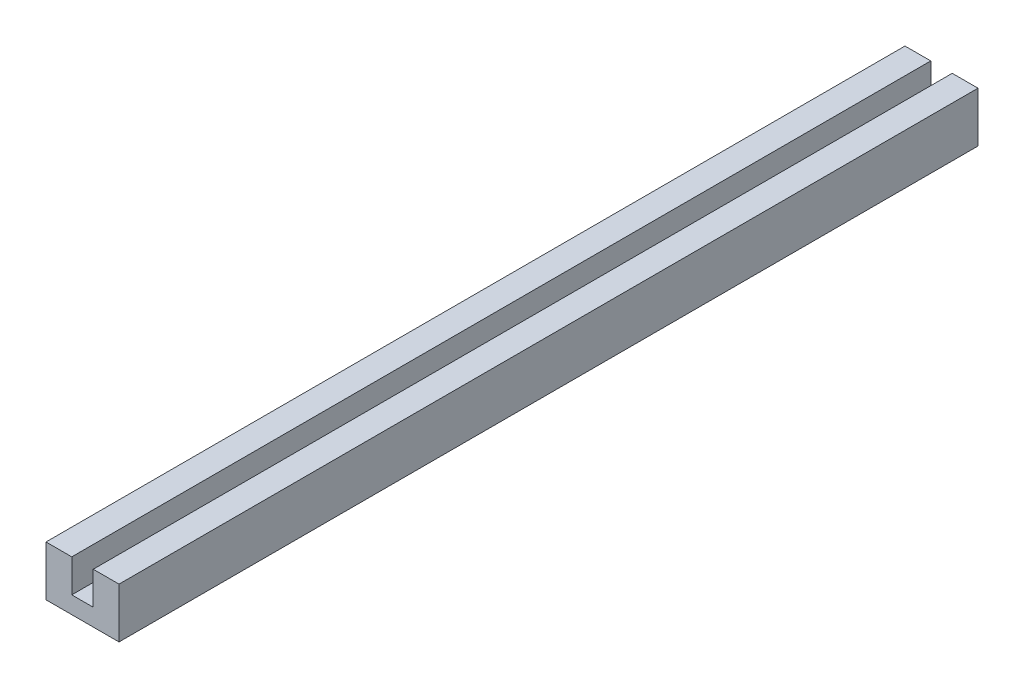
SolidWorks part; units mm, degrees
ref_plane "Front Plane" through (0, 0, 0) normal (0, 0, 1) x (1, 0, 0)
ref_plane "Top Plane" through (0, 0, 0) normal (0, 1, 0) x (1, 0, 0)
ref_plane "Right Plane" through (0, 0, 0) normal (1, 0, 0) x (0, 0, -1)
sketch "Sketch2" plane through (0, 0, 0) normal (0, 0, 1) x (1, 0, 0)
  line L0 (0, 0) -> (5.1, 0)
  line L1 (5.1, 0) -> (5.1, 3.5)
  line L2 (5.1, 3.5) -> (3.3, 3.5)
  line L3 (3.3, 3.5) -> (3.3, 1.2)
  line L4 (3.3, 1.2) -> (1.8, 1.2)
  line L5 (1.8, 1.2) -> (1.8, 3.5)
  line L6 (1.8, 3.5) -> (0, 3.5)
  line L7 (0, 3.5) -> (0, 0)
  dimension "D1" = 1.5
  dimension "D2" = 3.5
  dimension "D3" = 1.2
  dimension "D4" = 1.8
extrude "Boss-Extrude1" add sketch "Sketch2" along normal blind 60 contours L4 L5 L6 L7 L0 L1 L2 L3
equation "\"PCBThickness\"= 1.5"
equation "\"RailThickness\"= 1.25"
equation "\"RailDepth\" = 3.5"
